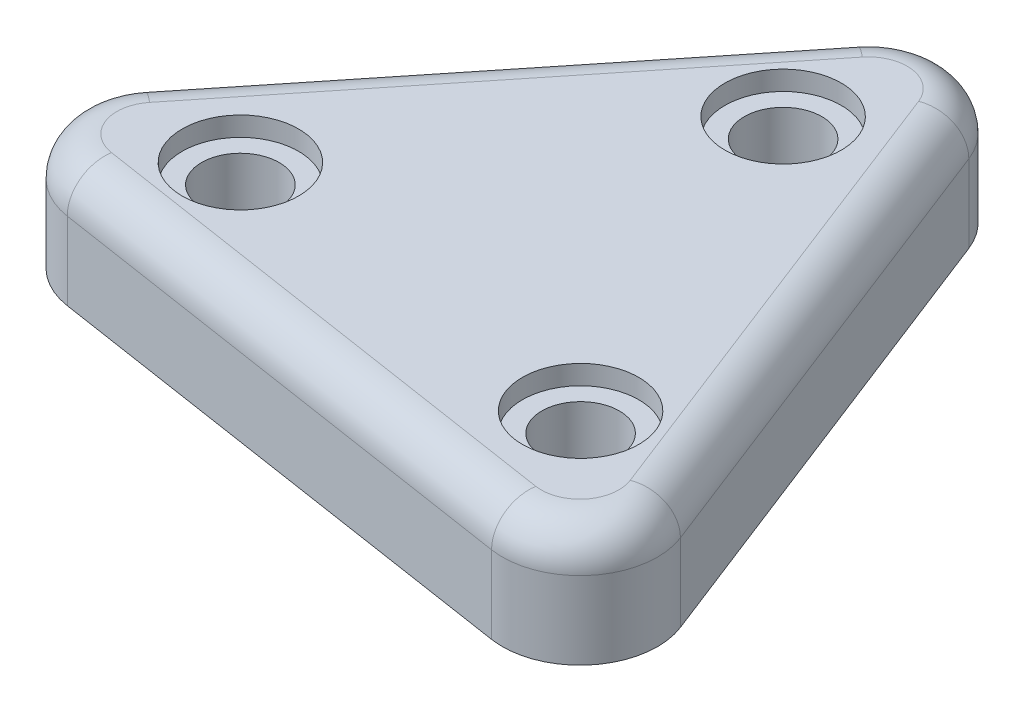
SolidWorks part; units mm, degrees
material "ABS"
ref_plane "Front Plane" through (0, 0, 0) normal (0, 0, 1) x (1, 0, 0)
ref_plane "Top Plane" through (0, 0, 0) normal (0, 1, 0) x (1, 0, 0)
ref_plane "Right Plane" through (0, 0, 0) normal (1, 0, 0) x (0, 0, -1)
sketch "Sketch1" plane through (0, 0, 0) normal (0, 1, 0) x (1, 0, 0)
  line L1 (0.6704, 5.7344) -> (-5.3014, -2.2866) construction
  line L2 (-5.3014, -2.2866) -> (4.631, -3.4478) construction
  line L3 (4.631, -3.4478) -> (0.6704, 5.7344) construction
  line L4 (1.7502, 11.4136) -> (-10.7596, -4.191)
  line L5 (-10.7596, -4.191) -> (9.0093, -7.2226)
  line L6 (9.0093, -7.2226) -> (1.7502, 11.4136)
  circle A0 centre (0, 0) radius 2.8868 construction
  circle A1 centre (0.6704, 5.7344) radius 1
  circle A2 centre (4.631, -3.4478) radius 1
  circle A3 centre (-5.3014, -2.2866) radius 1
  circle A4 centre (0, 0) radius 5.7735 construction
extrude "Boss-Extrude1" add sketch "Sketch1" along normal blind 3
fillet "Fillet1" radius 2 3 edges at (1.7502, 1.5, -11.4136) (9.0093, 1.5, 7.2226) (-10.7596, 1.5, 4.191)
fillet "Fillet2" radius 1 6 edges at (-8.896, 3, 3.4651) (-4.5047, 3, -3.6113) (1.4471, 3, -9.4367) (5.3798, 3, -2.0955) (7.4489, 3, 5.9716) (-0.8751, 3, 5.7068)
sketch "Sketch2" plane through (0, 3, 0) normal (0, 1, 0) x (1, 0, 0)
  circle A0 centre (0.6704, 5.7344) radius 1.5
  circle A1 centre (-5.3014, -2.2866) radius 1.5
  circle A2 centre (4.631, -3.4478) radius 1.5
extrude "Cut-Extrude1" cut sketch "Sketch2" against normal blind 0.5
